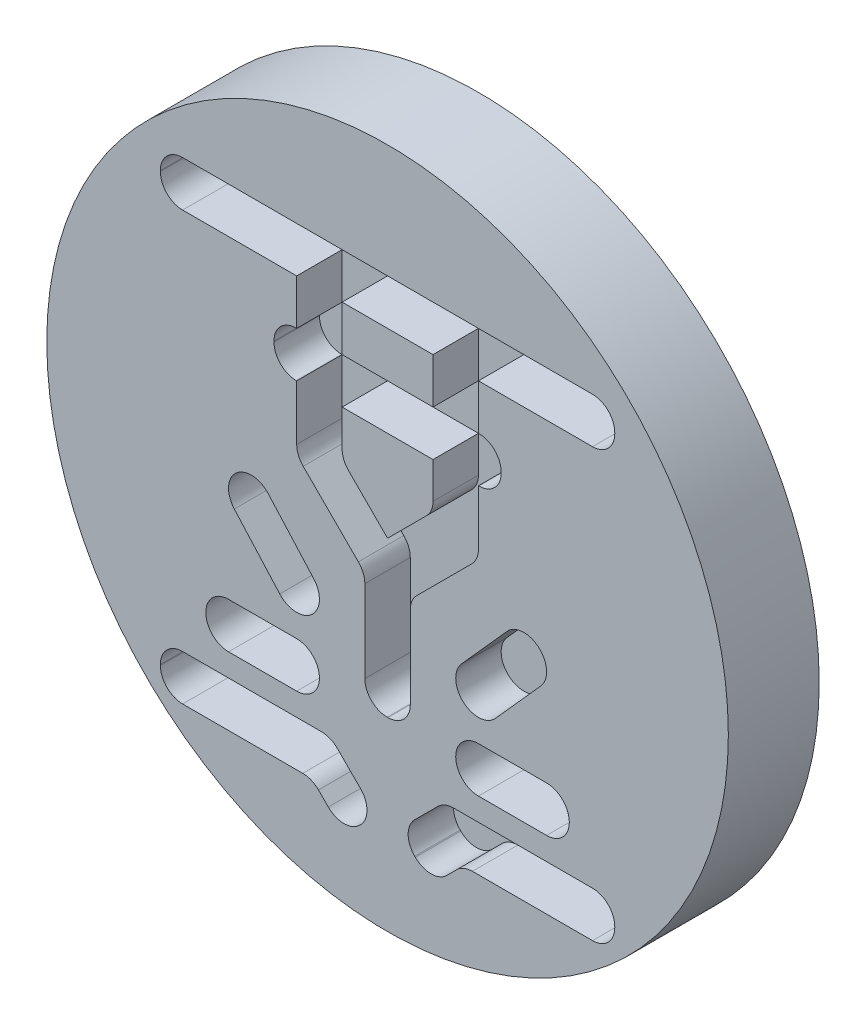
SolidWorks part; units mm, degrees
ref_plane "Front Plane" through (0, 0, 0) normal (0, 0, 1) x (1, 0, 0)
ref_plane "Top Plane" through (0, 0, 0) normal (0, 1, 0) x (1, 0, 0)
ref_plane "Right Plane" through (0, 0, 0) normal (1, 0, 0) x (0, 0, -1)
sketch "Sketch1" plane through (0, 0, 0) normal (0, 0, 1) x (1, 0, 0)
  line L1 (-18.5, -17.5) -> (18.5, -17.5)
  line L2 (-18.5, -17.5) -> (-18.5, 17.5)
  line L3 (-18.5, 17.5) -> (18.5, 17.5)
  line L4 (18.5, -17.5) -> (18.5, 17.5)
  line L5 (-18.5, -17.5) -> (18.5, 17.5) construction
  line L6 (-18.5, 17.5) -> (18.5, -17.5) construction
  point P0 (0, 0)
  dimension "D1" = 37
  dimension "D2" = 35
extrude "Boss-Extrude1" add sketch "Sketch1" along normal blind 24
sketch "Sketch2" plane through (0, 0, 24) normal (0, 0, 1) x (1, 0, 0)
  line L0 (18.5, 11.5) -> (16.5, 11.5)
  line L1 (18.5, 17.5) -> (16.5, 17.5)
  line L2 (18.5, 17.5) -> (18.5, 15.5)
  line L3 (18.5, 15.5) -> (16.5, 15.5)
  line L4 (16.5, 17.5) -> (16.5, 15.5)
  line L5 (18.5, -17.5) -> (18.5, 17.5) construction
  line L6 (16.5, 11.5) -> (16.5, 4.5)
  line L7 (16.5, 4.5) -> (13.5, 4.5)
  line L8 (13.5, 4.5) -> (13.5, -17.5)
  line L9 (-18.5, -17.5) -> (18.5, -17.5) construction
  line L10 (13.5, -17.5) -> (18.5, -17.5)
  line L11 (18.5, -17.5) -> (18.5, 11.5)
  line L12 (-18.5, 11.5) -> (-16.5, 11.5)
  line L13 (-18.5, 17.5) -> (-18.5, -17.5) construction
  line L14 (-16.5, 11.5) -> (-16.5, 4.5)
  line L15 (-16.5, 4.5) -> (-13.5, 4.5)
  line L16 (-13.5, 4.5) -> (-13.5, -17.5)
  line L17 (-13.5, -17.5) -> (-18.5, -17.5)
  line L18 (-18.5, -17.5) -> (-18.5, 11.5)
  line L20 (-18.5, 17.5) -> (-16.5, 17.5)
  line L21 (-18.5, 17.5) -> (-18.5, 15.5)
  line L22 (-18.5, 15.5) -> (-16.5, 15.5)
  line L23 (-16.5, 17.5) -> (-16.5, 15.5)
  circle A0 centre (-12.5, 11.5) radius 1.7
  circle A1 centre (12.5, 11.5) radius 1.7
  circle A2 centre (0, -8.5) radius 10.5
  dimension "D6" = 3.4
  dimension "D11" = 21
  dimension "D1" = 2
  dimension "D2" = 2
  dimension "D3" = 4
  dimension "D4" = 13
  dimension "D5" = 3
  dimension "D7" = 25
  dimension "D8" = 12.5
  dimension "D9" = 6
  dimension "D10" = 26
extrude "Cut-Extrude1" cut sketch "Sketch2" against normal through all
sketch "Sketch3" plane through (-18.5, 0, 0) normal (-1, 0, 0) x (0, 0, 1)
  line L0 (5, 17.5) -> (8, 14.5)
  line L1 (0, 17.5) -> (24, 17.5) construction
  line L2 (8, 14.5) -> (16, 14.5)
  line L3 (16, 14.5) -> (19, 17.5)
  line L4 (19, 17.5) -> (5, 17.5)
  dimension "D1" = 5
  dimension "D2" = 5
  dimension "D3" = 3
  dimension "D4" = 8
  dimension "D5" = 8
extrude "Cut-Extrude2" cut sketch "Sketch3" against normal blind 3
sketch "Sketch4" plane through (0, 0, 24) normal (0, 0, 1) x (1, 0, 0)
  circle A0 centre (-10, 1.5) radius 2.05
  circle A1 centre (10, 1.5) radius 2.05
  dimension "D1" = 4.1
  dimension "D2" = 20
  dimension "D3" = 16
  dimension "D4" = 10
extrude "Cut-Extrude3" cut sketch "Sketch4" against normal blind 5
sketch "Sketch5" plane through (0, 17.5, 0) normal (0, 1, 0) x (1, 0, 0)
  circle A0 centre (0, -12) radius 6.25
  dimension "D2" = 12.5
  dimension "D1" = 12
extrude "Cut-Extrude4" cut sketch "Sketch5" against normal through all
sketch "Sketch6" plane through (0, 17.5, 0) normal (0, 1, 0) x (1, 0, 0)
  circle A0 centre (0, -12) radius 8.25
  dimension "D1" = 16.5
extrude "Cut-Extrude5" cut sketch "Sketch6" against normal blind 4.5
sketch "Sketch7" plane through (0, -17.5, 0) normal (0, -1, 0) x (-1, 0, 0)
  circle A0 centre (0, -12) radius 11.5
  dimension "D1" = 23
extrude "Cut-Extrude6" cut sketch "Sketch7" against normal blind 19
sketch "Sketch8" plane through (0, 0, 24) normal (0, 0, 1) x (1, 0, 0)
  line L0 (-16.5, 4.5) -> (-16.5, 11.5) construction
  line L1 (-16.5, 8.5) -> (-14.5, 8.5)
  line L2 (-16.5, 8.5) -> (-16.5, 5.5)
  line L3 (-16.5, 5.5) -> (-10.5, 5.5)
  line L4 (-10.5, 8.5) -> (-10.5, 5.5)
  line L5 (16.5, 11.5) -> (16.5, 4.5) construction
  line L6 (16.5, 8.5) -> (14.5, 8.5)
  line L7 (16.5, 8.5) -> (16.5, 5.5)
  line L8 (16.5, 5.5) -> (10.5, 5.5)
  line L9 (10.5, 8.5) -> (10.5, 5.5)
  line L10 (-10.5, 8.5) -> (-10.5, 9.2639)
  line L12 (-14.5, 9.2639) -> (-14.5, 8.5)
  line L13 (10.5, 8.5) -> (10.5, 9.2639)
  line L15 (14.5, 9.2639) -> (14.5, 8.5)
  arc A0 (-10.5, 9.2639) -> (-14.5, 9.2639) centre (-12.5, 11.5) ccw
  arc A1 (14.5, 9.2639) -> (10.5, 9.2639) centre (12.5, 11.5) ccw
  dimension "D1" = 6
  dimension "D2" = 6
  dimension "D3" = 12
  dimension "D4" = 3
  dimension "D5" = 4
  dimension "D6" = 4
extrude "Cut-Extrude7" cut sketch "Sketch8" against normal blind 6
sketch "Sketch9" plane through (0, 1.5, 0) normal (0, -1, 0) x (-1, 0, 0)
  circle A0 centre (0, -12) radius 8.25
  dimension "D1" = 16.5
extrude "Cut-Extrude8" cut sketch "Sketch9" against normal blind 5.25
sketch "Sketch10" plane through (0, 0, 0) normal (0, 0, -1) x (-1, 0, 0)
  line L0 (-8.5, 17.5) -> (-8.5, -2.3356)
  line L1 (-16.5, 17.5) -> (16.5, 17.5) construction
  line L2 (-8.5, -2.3356) -> (8.5, -2.3356)
  line L3 (8.5, -2.3356) -> (8.5, 17.5)
  line L4 (8.5, 17.5) -> (4.5, 17.5)
  line L5 (4.5, 17.5) -> (4.5, 1.5)
  line L6 (4.5, 1.5) -> (-4.5, 1.5)
  line L7 (-4.5, 1.5) -> (-4.5, 17.5)
  line L8 (-4.5, 17.5) -> (-8.5, 17.5)
  arc A0 (5.4083, -17.5) -> (-5.4083, -17.5) centre (0, -8.5) ccw construction
  dimension "D1" = 8
  dimension "D2" = 4
  dimension "D3" = 4
  dimension "D4" = 16
extrude "Cut-Extrude9" cut sketch "Sketch10" against normal blind 4
fillet "Fillet1" radius 2 4 edges at (8.5, 7.5822, 4) (4.5, 9.5, 4) (-8.5, 7.5822, 4) (-4.5, 9.5, 4)
fillet "Fillet2" radius 2 4 edges at (5.4083, -17.5, 0.9256) (5.4083, -17.5, 23.0744) (-5.4083, -17.5, 23.0744) (-5.4083, -17.5, 0.9256)
sketch "Sketch11" plane through (0, 17.5, 0) normal (0, 1, 0) x (1, 0, 0)
  line L0 (18.5, 0) -> (18.5, -24) construction
  line L1 (-18.5, 0) -> (18.5, 0)
  line L2 (-18.5, 0) -> (-18.5, -12)
  line L3 (-18.5, -12) -> (18.5, -12)
  line L4 (18.5, 0) -> (18.5, -12)
  dimension "D1" = 12
extrude "Cut-Extrude10" cut sketch "Sketch11" against normal through all
fillet "Fillet3" radius 0.5 34 edges at (11.2104, -17.5, 14.5646) (8.3996, -15.9145, 19.8547) (-11.2104, -17.5, 14.5646) (-8.505, -16.2571, 19.7405) (16.5, 7, 18) (-16.5, 7, 18) (-16.5, 8.5, 21) (-16.5, 5.5, 21) (16.5, 8.5, 21) (16.5, 5.5, 21) (10.5, 5.5, 21) (10.5, 9.2639, 21) (-10.5, 9.2639, 21) (-10.5, 5.5, 21) (-14.5, 8.5, 21) (-14.5, 9.2639, 21) (14.5, 9.2639, 21) (14.5, 8.5, 21) (16.5, 17.5, 18) (18.5, 15.5, 18) (18.5, 11.5, 18) (16.5, 4.5, 18) (13.5, 4.5, 18) (-13.5, 4.5, 18) (-16.5, 4.5, 18) (10.2884, -6.4026, 17.138) (-18.5, 11.5, 18) (-18.5, 15.5, 20.5) (-16.5, 17.5, 21.5) (-16.5, 16.5, 18) (-10.3896, -6.9812, 16.9302) (-16, 17.5, 19) (-15.5, 17.5, 15.5) (0, 17.5, 20.25)
fillet "Fillet4" radius 0.5 4 edges at (-6.873, 1.5, 16.5634) (6.873, 1.5, 16.5634) (0, 6.75, 18.25) (0, 13, 18.25)
fillet "Fillet5" radius 1 2 edges at (13.5, -17.5, 18) (-13.5, -17.5, 18)
sketch "Sketch12" plane through (0, 0, 24) normal (0, 0, 1) x (1, 0, 0)
  line L0 (-4.51, 16) -> (4.51, 16)
  line L1 (5, 15.51) -> (5, 15.49)
  line L2 (4.51, 15) -> (2, 15)
  line L3 (2, 15) -> (2, 14)
  line L4 (2, 14) -> (2.01, 14)
  line L5 (2.5, 13.51) -> (2.5, 13.49)
  line L6 (2.01, 13) -> (2, 13)
  line L7 (2, 13) -> (2, 11.7888)
  line L8 (1.8565, 11.4423) -> (0.6435, 10.2293)
  line L9 (0.5, 9.8828) -> (0.5, 8.0758)
  line L10 (0.01, 7.5858) -> (-0.01, 7.5858)
  line L11 (-0.5, 8.0758) -> (-0.5, 9.8828)
  line L12 (-0.6435, 10.2293) -> (-1.8565, 11.4423)
  line L13 (-2, 11.7888) -> (-2, 13)
  line L14 (-2, 13) -> (-2.01, 13)
  line L15 (-2.5, 13.49) -> (-2.5, 13.51)
  line L16 (-2.01, 14) -> (-2, 14)
  line L17 (-2, 14) -> (-2, 15)
  line L18 (-2, 15) -> (-4.51, 15)
  line L19 (-5, 15.49) -> (-5, 15.51)
  line L20 (-1, 13) -> (-1, 12.203)
  line L21 (-1, 15) -> (1, 15)
  line L22 (-1, 15) -> (-1, 14)
  line L23 (-1, 14) -> (1, 14)
  line L24 (1, 15) -> (1, 14)
  line L25 (-0.8565, 11.8565) -> (0, 11)
  line L26 (0, 11) -> (0.8565, 11.8565)
  line L27 (1, 12.203) -> (1, 13)
  line L28 (1, 13) -> (-1, 13)
  line L29 (-2, 9.0858) -> (-3, 10.2038) construction
  line L30 (-2.3727, 8.7525) -> (-3.3727, 9.8705)
  line L31 (-1.6273, 9.4191) -> (-2.6273, 10.5372)
  line L32 (2, 9.0858) -> (3, 10.2038) construction
  line L33 (1.6273, 9.4191) -> (2.6273, 10.5372)
  line L34 (2.3727, 8.7525) -> (3.3727, 9.8705)
  line L35 (2, 7.5858) -> (3.5, 7.5858) construction
  line L36 (2, 8.0858) -> (3.5, 8.0858)
  line L37 (2, 7.0858) -> (3.5, 7.0858)
  line L38 (-2, 7.5858) -> (-3.5, 7.5858) construction
  line L39 (-2, 7.0858) -> (-3.5, 7.0858)
  line L40 (-2, 8.0858) -> (-3.5, 8.0858)
  line L41 (-4.51, 6.5858) -> (-1.453, 6.5858)
  line L42 (-1.1065, 6.4423) -> (-0.5965, 5.9323)
  line L43 (-0.5965, 5.2393) -> (-0.6106, 5.2252)
  line L44 (-1.3036, 5.2252) -> (-1.5207, 5.4423)
  line L45 (-1.8672, 5.5858) -> (-4.51, 5.5858)
  line L46 (-5, 6.0758) -> (-5, 6.0958)
  line L47 (1.453, 6.5858) -> (4.51, 6.5858)
  line L48 (5, 6.0958) -> (5, 6.0758)
  line L49 (4.51, 5.5858) -> (1.8672, 5.5858)
  line L50 (1.5207, 5.4423) -> (1.3036, 5.2252)
  line L51 (0.6106, 5.2252) -> (0.5965, 5.2393)
  line L52 (0.5965, 5.9323) -> (1.1065, 6.4423)
  line L53 (16, 17.5) -> (-16, 17.5) construction
  arc A0 (-2.3727, 8.7525) -> (-1.6273, 9.4191) centre (-2, 9.0858) ccw
  arc A1 (-2.6273, 10.5372) -> (-3.3727, 9.8705) centre (-3, 10.2038) ccw
  arc A2 (1.6273, 9.4191) -> (2.3727, 8.7525) centre (2, 9.0858) ccw
  arc A3 (3.3727, 9.8705) -> (2.6273, 10.5372) centre (3, 10.2038) ccw
  arc A4 (2, 8.0858) -> (2, 7.0858) centre (2, 7.5858) ccw
  arc A5 (3.5, 7.0858) -> (3.5, 8.0858) centre (3.5, 7.5858) ccw
  arc A6 (-2, 7.0858) -> (-2, 8.0858) centre (-2, 7.5858) ccw
  arc A7 (-3.5, 8.0858) -> (-3.5, 7.0858) centre (-3.5, 7.5858) ccw
  arc A8 (0.6435, 10.2293) -> (0.5, 9.8828) centre (0.99, 9.8828) ccw
  arc A9 (2, 11.7888) -> (1.8565, 11.4423) centre (1.51, 11.7888) cw
  arc A10 (0.8565, 11.8565) -> (1, 12.203) centre (0.51, 12.203) ccw
  arc A11 (-1, 12.203) -> (-0.8565, 11.8565) centre (-0.51, 12.203) ccw
  arc A12 (-1.8565, 11.4423) -> (-2, 11.7888) centre (-1.51, 11.7888) cw
  arc A13 (-0.5, 9.8828) -> (-0.6435, 10.2293) centre (-0.99, 9.8828) ccw
  arc A14 (-1.453, 6.5858) -> (-1.1065, 6.4423) centre (-1.453, 6.0958) cw
  arc A15 (-1.5207, 5.4423) -> (-1.8672, 5.5858) centre (-1.8672, 5.0958) ccw
  arc A16 (1.8672, 5.5858) -> (1.5207, 5.4423) centre (1.8672, 5.0958) ccw
  arc A17 (1.453, 6.5858) -> (1.1065, 6.4423) centre (1.453, 6.0958) ccw
  arc A18 (5, 6.0758) -> (4.51, 5.5858) centre (4.51, 6.0758) cw
  arc A19 (4.51, 6.5858) -> (5, 6.0958) centre (4.51, 6.0958) cw
  arc A20 (-4.51, 6.5858) -> (-5, 6.0958) centre (-4.51, 6.0958) ccw
  arc A21 (-4.51, 5.5858) -> (-5, 6.0758) centre (-4.51, 6.0758) cw
  arc A22 (-0.6106, 5.2252) -> (-1.3036, 5.2252) centre (-0.9571, 5.5716) cw
  arc A23 (-0.5965, 5.9323) -> (-0.5965, 5.2393) centre (-0.943, 5.5858) cw
  arc A24 (1.3036, 5.2252) -> (0.6106, 5.2252) centre (0.9571, 5.5716) cw
  arc A25 (0.5965, 5.2393) -> (0.5965, 5.9323) centre (0.943, 5.5858) cw
  arc A26 (0.5, 8.0758) -> (0.01, 7.5858) centre (0.01, 8.0758) cw
  arc A27 (-0.01, 7.5858) -> (-0.5, 8.0758) centre (-0.01, 8.0758) cw
  arc A28 (-2.5, 13.51) -> (-2.01, 14) centre (-2.01, 13.51) cw
  arc A29 (-2.01, 13) -> (-2.5, 13.49) centre (-2.01, 13.49) cw
  arc A30 (2.5, 13.49) -> (2.01, 13) centre (2.01, 13.49) cw
  arc A31 (2.01, 14) -> (2.5, 13.51) centre (2.01, 13.51) cw
  arc A32 (4.51, 15) -> (5, 15.49) centre (4.51, 15.49) ccw
  arc A33 (5, 15.51) -> (4.51, 16) centre (4.51, 15.51) ccw
  arc A34 (-5, 15.49) -> (-4.51, 15) centre (-4.51, 15.49) ccw
  arc A35 (-5, 15.51) -> (-4.51, 16) centre (-4.51, 15.51) cw
  point P31 (-2.5, 9.6448)
  point P36 (2.5, 9.6448)
  point P43 (2.75, 7.5858)
  point P50 (-2.75, 7.5858)
  point P166 (0.5, 10.0858)
  point P169 (2, 11.5858)
  point P172 (1, 12)
  point P175 (-1, 12)
  point P178 (-2, 11.5858)
  point P181 (-0.5, 10.0858)
  point P184 (-1.25, 6.5858)
  point P191 (1.25, 6.5858)
  point P194 (5, 5.5858)
  point P197 (5, 6.5858)
  point P200 (-5, 6.5858)
  point P203 (-5, 5.5858)
  point P208 (-0.25, 5.5858)
  point P213 (0.25, 5.5858)
  point P216 (0.5, 7.5858)
  point P219 (-0.5, 7.5858)
  point P222 (-2.5, 14)
  point P227 (2.5, 13)
  point P230 (2.5, 14)
  point P233 (5, 15)
  point P236 (5, 16)
  point P241 (-5, 16)
  dimension "D17" = 0.5
  dimension "D18" = 1.5
  dimension "D40" = 0.49
  dimension "D1" = 1
  dimension "D2" = 1
  dimension "D3" = 10
  dimension "D4" = 5
  dimension "D5" = 1
  dimension "D6" = 1
  dimension "D7" = 1
  dimension "D8" = 1
  dimension "D9" = 2
  dimension "D10" = 1
  dimension "D11" = 0.5
  dimension "D12" = 0.5
  dimension "D13" = 1
  dimension "D14" = 1
  dimension "D15" = 1
  dimension "D16" = 1.5
  dimension "D19" = 1.5
  dimension "D20" = 1.5
  dimension "D21" = 1.5
  dimension "D22" = 1
  dimension "D23" = 1
  dimension "D24" = 1
  dimension "D25" = 1
  dimension "D26" = 1
  dimension "D27" = 1
  dimension "D28" = 1
  dimension "D29" = 1
  dimension "D30" = 1
  dimension "D31" = 1.5
  dimension "D32" = 1.5
  dimension "D33" = 1.5
  dimension "D34" = 10
  dimension "D35" = 5
  dimension "D36" = 0.25
  dimension "D37" = 0.25
  dimension "D38" = 1
  dimension "D39" = 2.5
extrude "Cut-Extrude11" cut sketch "Sketch12" against normal blind 1
fillet "Fillet7" radius 0.5 10 edges at (7.5, 13, 12) (6.3964, 12.8536, 12) (-7.5, 13, 12) (-6.3964, 12.8536, 12) (6.25, 9.875, 12) (-6.25, 9.875, 12) (7.5, 6.75, 12) (6.3964, 6.8964, 12) (-7.5, 6.75, 12) (-6.3964, 6.8964, 12)
sketch "Sketch15" plane through (0, 17.5, 0) normal (0, 1, 0) x (1, 0, 0)
  line L0 (-16.5, -24) -> (-16.5, -18)
  line L1 (-16.5, -19.2071) -> (-16.5, -17.7071) construction
  line L2 (-16.5, -18) -> (-18.5, -18)
  line L3 (-18.5, -24) -> (-18.5, -16.5) construction
  line L4 (-18.5, -18) -> (-18.5, -24)
  line L5 (-18.5, -24) -> (-16.5, -24)
  line L6 (18.5, -12) -> (18.5, -24) construction
  line L7 (16.5, -24) -> (18.5, -24)
  line L8 (16.5, -24) -> (16.5, -18)
  line L9 (16.5, -18) -> (18.5, -18)
  line L10 (18.5, -24) -> (18.5, -18)
  dimension "D1" = 6
  dimension "D2" = 6
extrude "Cut-Extrude15" cut sketch "Sketch15" against normal through all
sketch "Sketch17" plane through (0, 17.5, 0) normal (0, 1, 0) x (1, 0, 0)
  line L0 (-16.5, -18) -> (-18.5, -16)
  line L1 (-18.5, -12) -> (-18.5, -16) construction
  line L2 (-18.5, -16) -> (-18.5, -18)
  line L3 (-18.5, -18) -> (-16.5, -18)
  line L4 (16.5, -18) -> (18.5, -16)
  line L5 (16.5, -12) -> (16.5, -24) construction
  line L6 (18.5, -12) -> (18.5, -18) construction
  line L7 (18.5, -16) -> (18.5, -18)
  line L8 (18.5, -18) -> (16.5, -18)
  dimension "D1" = 2
  dimension "D2" = 2
extrude "Cut-Extrude16" cut sketch "Sketch17" against normal through all
fillet "Fillet8" radius 0.5 8 edges at (17.25, 11.5, 17.25) (18.3536, 11.6464, 16.1464) (17.25, 15.5, 17.25) (18.3536, 15.3536, 16.1464) (-17.25, 11.5, 17.25) (-18.3536, 11.6464, 16.1464) (18.5, 13.5, 16) (-18.5, 13.25, 16)
fillet "Fillet9" radius 0.5 1 edges at (-17, 15.5, 17.5)
sketch "Sketch18" plane through (0, 0, 23) normal (0, 0, 1) x (1, 0, 0)
  circle A0 centre (0, 11) radius 7.5
  point P2 (0, 11)
  dimension "D1" = 15
extrude "Cut-Extrude17" cut sketch "Sketch18" against normal blind 20 and the other way blind 20 flip side to cut
sketch "Sketch20" plane through (0, 17.5, 0) normal (0, 1, 0) x (1, 0, 0)
  line L0 (-7.5, -12) -> (-7.5, -24) construction
  line L1 (-7.5, -22) -> (8.1889, -22)
  line L2 (-7.5, -22) -> (-7.5, -11.3937)
  line L3 (-7.5, -11.3937) -> (8.1889, -11.3937)
  line L4 (8.1889, -22) -> (8.1889, -11.3937)
  dimension "D1" = 2
extrude "Cut-Extrude19" cut sketch "Sketch20" against normal blind 20
sketch "Sketch21" plane through (0, 0, 24) normal (0, 0, 1) x (1, 0, 0)
  line L0 (-3.7417, 17.5) -> (3.7417, 17.5)
  arc A0 (3.7417, 17.5) -> (-3.7417, 17.5) centre (0, 11) ccw
extrude "Boss-Extrude2" add sketch "Sketch21" against normal up to surface (2 mm away) up to face at (0, 10.5, 22)
